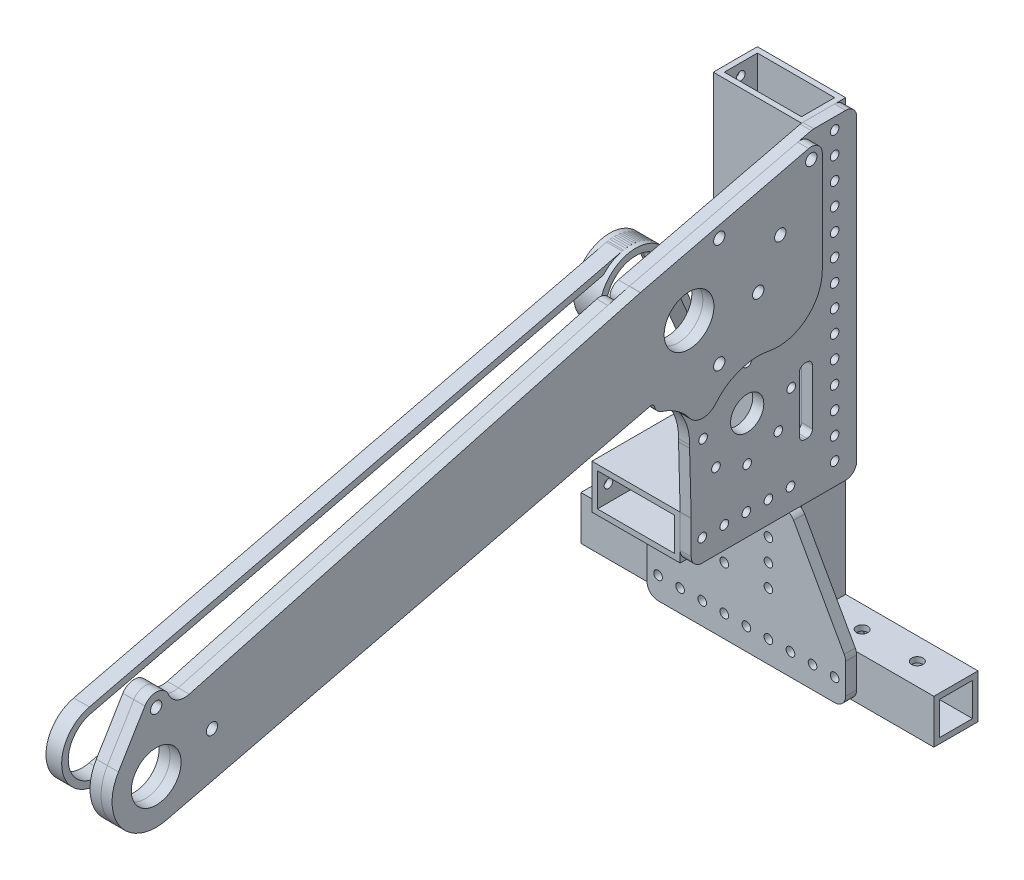
SolidWorks part; units mm, degrees
ref_plane "Alzado" through (0, 0, 0) normal (0, 0, 1) x (1, 0, 0)
ref_plane "Planta" through (0, 0, 0) normal (0, 1, 0) x (1, 0, 0)
ref_plane "Vista lateral" through (0, 0, 0) normal (1, 0, 0) x (0, 0, -1)
sketch "Croquis1" plane through (0, 0, 0) normal (0, 1, 0) x (1, 0, 0)
  line L1 (-101.6, -12.7) -> (101.6, -12.7)
  line L2 (-101.6, -12.7) -> (-101.6, 12.7)
  line L3 (-101.6, 12.7) -> (101.6, 12.7)
  line L4 (101.6, -12.7) -> (101.6, 12.7)
  line L5 (-101.6, -12.7) -> (101.6, 12.7) construction
  line L6 (-101.6, 12.7) -> (101.6, -12.7) construction
  point P0 (0, 0)
  dimension "D1" = 25.4
  dimension "D2" = 203.2
extrude "Saliente-Extruir1" add sketch "Croquis1" along normal blind 25.4
shell "Vaciado1" thickness 3.175 removed face at (-101.6, 12.7, 0) removed face at (101.6, 12.7, 0)
sketch "Croquis2" plane through (0, 25.4, 0) normal (0, 1, 0) x (1, 0, 0)
  line L0 (101.6, 12.7) -> (-101.6, 12.7) construction
  line L1 (-25.4, -12.7) -> (25.4, -12.7)
  line L2 (-25.4, -12.7) -> (-25.4, 12.7)
  line L3 (-25.4, 12.7) -> (25.4, 12.7)
  line L4 (25.4, -12.7) -> (25.4, 12.7)
  line L5 (-25.4, -12.7) -> (25.4, 12.7) construction
  line L6 (-25.4, 12.7) -> (25.4, -12.7) construction
  line L8 (-22.225, -9.525) -> (22.225, -9.525)
  line L9 (-22.225, -9.525) -> (-22.225, 9.525)
  line L10 (-22.225, 9.525) -> (22.225, 9.525)
  line L11 (22.225, -9.525) -> (22.225, 9.525)
  line L12 (-22.225, -9.525) -> (22.225, 9.525) construction
  line L13 (-22.225, 9.525) -> (22.225, -9.525) construction
  point P0 (0, 0)
  point P8 (0, 0)
  dimension "D1" = 50.8
  dimension "D2" = 3.175
  dimension "D3" = 3.175
extrude "Saliente-Extruir2" add sketch "Croquis2" along normal blind 247.65 separate body
sketch "Croquis3" plane through (0, 25.4, 0) normal (0, 1, 0) x (1, 0, 0)
  line L0 (0, 0) -> (0, 12.7) construction
  line L1 (25.4, 12.7) -> (-25.4, 12.7) construction
  circle A0 centre (-47.625, 0) radius 3.2639
  circle A1 centre (-79.375, 0) radius 3.2639
  circle A2 centre (79.375, 0) radius 3.2639
  circle A3 centre (47.625, 0) radius 3.2639
  dimension "D1" = 47.625
  dimension "D2" = 6.5278
  dimension "D3" = 31.75
extrude "Cortar-Extruir1" cut sketch "Croquis3" against normal through all
sketch "Croquis4" plane through (0, 0, 12.7) normal (0, 0, 1) x (1, 0, 0)
  line L0 (0, 25.4) -> (0, 139.6619) construction
  line L1 (-101.6, 25.4) -> (101.6, 25.4) construction
  line L2 (0, 139.6619) -> (-23.8125, 139.6619) construction
  circle A0 centre (0, 139.6619) radius 14.3129
  circle A1 centre (0, 139.6619) radius 23.8125 construction
  circle A2 centre (-23.8125, 139.6619) radius 2.4892 construction
  circle A3 centre (-11.9062, 160.2841) radius 2.4892
  circle A4 centre (11.9063, 160.2841) radius 2.4892
  circle A5 centre (23.8125, 139.6619) radius 2.4892 construction
  circle A6 centre (11.9062, 119.0397) radius 2.4892
  circle A7 centre (-11.9063, 119.0397) radius 2.4892
  dimension "D1" = 28.6258
  dimension "D3" = 47.625
  dimension "D4" = 4.9784
  dimension "D2" = 114.2619
  dimension "D6" = 23.8125
  dimension "D5" = 6
extrude "Cortar-Extruir2" cut sketch "Croquis4" against normal through all
sketch "Croquis8" plane through (0, 0, 12.7) normal (0, 0, 1) x (1, 0, 0)
  line L0 (0, 0) -> (0, 273.05) construction
  line L1 (-101.6, 12.7) -> (0, 12.7) construction
  line L2 (-101.6, 25.4) -> (-101.6, 0) construction
  line L3 (0, 12.7) -> (-12.7, 12.7) construction
  line L4 (0, 12.7) -> (12.7, 12.7) construction
  line L5 (-25.4, 273.05) -> (25.4, 273.05) construction
  line L6 (-12.7, 12.7) -> (-12.7, 25.4) construction
  circle A0 centre (0, 12.7) radius 2.4892
  circle A1 centre (-12.7, 12.7) radius 2.4892
  circle A2 centre (-25.4, 12.7) radius 2.4892
  circle A3 centre (-38.1, 12.7) radius 2.4892
  circle A4 centre (-50.8, 12.7) radius 2.4892
  circle A5 centre (0, 12.7) radius 2.4892
  circle A6 centre (-12.7, 12.7) radius 2.4892
  circle A7 centre (-25.4, 12.7) radius 2.4892
  circle A8 centre (-38.1, 12.7) radius 2.4892
  circle A9 centre (12.7, 12.7) radius 2.4892
  circle A10 centre (0, 12.7) radius 2.4892
  circle A11 centre (-12.7, 12.7) radius 2.4892
  circle A12 centre (-25.4, 12.7) radius 2.4892
  circle A13 centre (25.4, 12.7) radius 2.4892
  circle A14 centre (12.7, 12.7) radius 2.4892
  circle A15 centre (0, 12.7) radius 2.4892
  circle A16 centre (-12.7, 12.7) radius 2.4892
  circle A17 centre (38.1, 12.7) radius 2.4892
  circle A18 centre (25.4, 12.7) radius 2.4892
  circle A19 centre (12.7, 12.7) radius 2.4892
  circle A20 centre (0, 12.7) radius 2.4892
  circle A21 centre (12.7, 12.7) radius 2.4892
  circle A22 centre (25.4, 12.7) radius 2.4892
  circle A23 centre (38.1, 12.7) radius 2.4892
  circle A24 centre (50.8, 12.7) radius 2.4892
  circle A25 centre (-12.7, 25.4) radius 2.4892 [skipped]
  circle A26 centre (12.7, 25.4) radius 2.4892 [skipped]
  circle A27 centre (-12.7, 38.1) radius 2.4892
  circle A28 centre (12.7, 38.1) radius 2.4892
  circle A29 centre (-12.7, 50.8) radius 2.4892
  circle A30 centre (12.7, 50.8) radius 2.4892
  circle A31 centre (-12.7, 63.5) radius 2.4892
  circle A32 centre (12.7, 63.5) radius 2.4892
  circle A33 centre (-12.7, 76.2) radius 2.4892
  circle A34 centre (12.7, 76.2) radius 2.4892
  dimension "D1" = 4.9784
  dimension "D4" = 12.7
  dimension "D5" = 12.7
  dimension "D7" = 12.7
  dimension "D2" = 5
  dimension "D3" = 5
  dimension "D6" = 6
extrude "Cortar-Extruir4" cut sketch "Croquis8" against normal through all contours A4 | A3 | A2 | A1 | A0 | A9 | A13 | A17 | A24 | A28 | A29 | A30 | A31 | A32 | A34 | A33 | A27 region at (0, 12.7, 12.7) region at (-12.7, 12.7, 12.7) region at (-25.4, 12.7, 12.7) region at (-38.1, 12.7, 12.7) region at (-50.8, 12.7, 12.7) region at (12.7, 12.7, 12.7) region at (25.4, 12.7, 12.7) region at (38.1, 12.7, 12.7) region at (50.8, 12.7, 12.7) region at (12.7, 38.1, 12.7) region at (-12.7, 50.8, 12.7) region at (12.7, 50.8, 12.7) region at (-12.7, 63.5, 12.7) region at (12.7, 63.5, 12.7) region at (-12.7, 76.2, 12.7) region at (12.7, 76.2, 12.7)
sketch "Croquis6" plane through (0, 0, 12.7) normal (0, 0, 1) x (1, 0, 0)
  line L0 (25.4, 273.05) -> (25.4, 25.4) construction
  line L1 (-25.4, 88.646) -> (25.4, 88.646)
  line L2 (-25.4, 88.646) -> (-25.4, 114.046)
  line L3 (-25.4, 114.046) -> (25.4, 114.046)
  line L4 (25.4, 88.646) -> (25.4, 114.046)
  line L5 (-25.4, 88.646) -> (25.4, 114.046) construction
  line L6 (-25.4, 114.046) -> (25.4, 88.646) construction
  line L7 (-101.6, 25.4) -> (101.6, 25.4) construction
  line L9 (-22.225, 91.821) -> (22.225, 91.821)
  line L10 (-22.225, 91.821) -> (-22.225, 110.871)
  line L11 (-22.225, 110.871) -> (22.225, 110.871)
  line L12 (22.225, 91.821) -> (22.225, 110.871)
  line L13 (-22.225, 91.821) -> (22.225, 110.871) construction
  line L14 (-22.225, 110.871) -> (22.225, 91.821) construction
  point P0 (0, 101.346)
  point P11 (0, 101.346)
  dimension "D1" = 25.4
  dimension "D2" = 63.246
  dimension "D3" = 3.175
  dimension "D4" = 3.175
extrude "Saliente-Extruir3" add sketch "Croquis6" along normal blind 69.85 separate body
sketch "Croquis7" plane through (0, 114.046, 0) normal (0, 1, 0) x (1, 0, 0)
  line L0 (0, -12.7) -> (0, -82.55) construction
  line L1 (-25.4, -12.7) -> (25.4, -12.7) construction
  line L2 (25.4, -82.55) -> (-25.4, -82.55) construction
  line L3 (16.51, -12.7) -> (-16.51, -12.7)
  line L4 (25.4, -12.7) -> (-25.4, -12.7) construction
  line L5 (-16.51, -12.7) -> (-16.51, -34.798)
  line L6 (-13.208, -38.1) -> (13.208, -38.1)
  line L7 (16.51, -12.7) -> (16.51, -34.798)
  arc A0 (16.51, -34.798) -> (13.208, -38.1) centre (13.208, -34.798) cw
  arc A1 (-16.51, -34.798) -> (-13.208, -38.1) centre (-13.208, -34.798) ccw
  point P12 (0, -38.1)
  point P16 (16.51, -38.1)
  point P19 (-16.51, -38.1)
  dimension "D3" = 3.302
  dimension "D1" = 25.4
  dimension "D2" = 33.02
extrude "Cortar-Extruir3" cut sketch "Croquis7" against normal up to next (3.175 mm away)
sketch "Croquis11" plane through (25.4, 0, 0) normal (1, 0, 0) x (0, 0, -1)
  line L0 (0, -101.854) -> (-381, -101.854) construction
  line L1 (-82.55, 88.646) -> (-82.55, 114.046) construction
  line L2 (-82.55, 88.646) -> (-12.7, 88.646) construction
  line L6 (-517.96, -101.854) -> (-276.66, -101.854) construction
  line L7 (-517.96, -101.854) -> (-517.96, 139.446) construction
  line L8 (-517.96, 139.446) -> (-276.66, 139.446) construction
  line L9 (-276.66, -101.854) -> (-276.66, 139.446) construction
  circle A0 centre (-396.875, 145.796) radius 38.1
  dimension "D3" = 76.2
  dimension "D4" = 209.55
  dimension "D5" = 276.225
  dimension "D1" = 190.5
  dimension "D2" = 381
  dimension "D6" = 241.3
sketch "Croquis9" plane through (0, 0, 12.7) normal (0, 0, 1) x (1, 0, 0)
  line L0 (0, 0) -> (0, 273.05) construction
  line L1 (-25.4, 273.05) -> (25.4, 273.05) construction
  line L2 (50.8, 0) -> (-50.8, 0)
  line L3 (-101.6, 0) -> (101.6, 0) construction
  line L4 (-57.15, 6.35) -> (-57.15, 23.7481)
  line L5 (-101.6, 25.4) -> (101.6, 25.4) construction
  line L6 (-56.3451, 26.8425) -> (-27.2168, 79.0403)
  line L7 (-25.4, 273.05) -> (-25.4, 25.4) construction
  line L8 (-21.6717, 82.296) -> (21.6717, 82.296)
  line L9 (56.3451, 26.8425) -> (27.2168, 79.0403)
  line L10 (57.15, 6.35) -> (57.15, 23.7481)
  line L11 (-25.4, 88.646) -> (25.4, 88.646) construction
  circle A0 centre (-50.8, 12.7) radius 2.4892 construction
  arc A2 (-50.8, 0) -> (-57.15, 6.35) centre (-50.8, 6.35) cw
  arc A3 (-57.15, 23.7481) -> (-56.3451, 26.8425) centre (-50.8, 23.7481) cw
  arc A4 (-27.2168, 79.0403) -> (-21.6717, 82.296) centre (-21.6717, 75.946) cw
  arc A5 (27.2168, 79.0403) -> (21.6717, 82.296) centre (21.6717, 75.946) ccw
  arc A6 (57.15, 23.7481) -> (56.3451, 26.8425) centre (50.8, 23.7481) ccw
  arc A7 (50.8, 0) -> (57.15, 6.35) centre (50.8, 6.35) ccw
  circle A9 centre (-25.4, 12.7) radius 2.4892
  circle A10 centre (-25.4, 12.7) radius 2.4892
  circle A11 centre (-12.7, 12.7) radius 2.4892
  circle A12 centre (-12.7, 12.7) radius 2.4892
  circle A13 centre (0, 12.7) radius 2.4892
  circle A14 centre (0, 12.7) radius 2.4892
  circle A15 centre (0, 12.7) radius 2.4892
  circle A16 centre (0, 12.7) radius 2.4892
  circle A17 centre (12.7, 12.7) radius 2.4892
  circle A18 centre (12.7, 12.7) radius 2.4892
  circle A19 centre (-38.1, 12.7) radius 2.4892
  circle A20 centre (-38.1, 12.7) radius 2.4892
  circle A21 centre (-25.4, 12.7) radius 2.4892
  circle A22 centre (-25.4, 12.7) radius 2.4892
  circle A23 centre (-12.7, 12.7) radius 2.4892
  circle A24 centre (-12.7, 12.7) radius 2.4892
  circle A25 centre (0, 12.7) radius 2.4892
  circle A26 centre (0, 12.7) radius 2.4892
  circle A27 centre (-50.8, 12.7) radius 2.4892
  circle A28 centre (-50.8, 12.7) radius 2.4892
  circle A29 centre (-38.1, 12.7) radius 2.4892
  circle A30 centre (-38.1, 12.7) radius 2.4892
  circle A31 centre (25.4, 12.7) radius 2.4892
  circle A32 centre (25.4, 12.7) radius 2.4892
  circle A33 centre (38.1, 12.7) radius 2.4892
  circle A34 centre (38.1, 12.7) radius 2.4892
  circle A35 centre (-12.7, 12.7) radius 2.4892
  circle A36 centre (-12.7, 12.7) radius 2.4892
  circle A37 centre (0, 12.7) radius 2.4892
  circle A38 centre (0, 12.7) radius 2.4892
  circle A39 centre (12.7, 12.7) radius 2.4892
  circle A40 centre (12.7, 12.7) radius 2.4892
  circle A41 centre (25.4, 12.7) radius 2.4892
  circle A42 centre (25.4, 12.7) radius 2.4892
  circle A43 centre (-25.4, 12.7) radius 2.4892
  circle A44 centre (-25.4, 12.7) radius 2.4892
  circle A45 centre (-12.7, 12.7) radius 2.4892
  circle A46 centre (-12.7, 12.7) radius 2.4892
  circle A47 centre (50.8, 12.7) radius 2.4892
  circle A48 centre (50.8, 12.7) radius 2.4892
  circle A49 centre (38.1, 12.7) radius 2.4892
  circle A50 centre (38.1, 12.7) radius 2.4892
  circle A51 centre (25.4, 12.7) radius 2.4892
  circle A52 centre (25.4, 12.7) radius 2.4892
  circle A53 centre (12.7, 12.7) radius 2.4892
  circle A54 centre (12.7, 12.7) radius 2.4892
  circle A55 centre (0, 12.7) radius 2.4892
  circle A56 centre (0, 12.7) radius 2.4892
  circle A57 centre (12.7, 12.7) radius 2.4892
  circle A58 centre (12.7, 12.7) radius 2.4892
  circle A59 centre (-12.7, 76.2) radius 2.4892
  circle A60 centre (-12.7, 76.2) radius 2.4892
  circle A61 centre (12.7, 63.5) radius 2.4892
  circle A62 centre (12.7, 63.5) radius 2.4892
  circle A63 centre (-12.7, 63.5) radius 2.4892
  circle A64 centre (-12.7, 63.5) radius 2.4892
  circle A65 centre (12.7, 50.8) radius 2.4892
  circle A66 centre (12.7, 50.8) radius 2.4892
  circle A67 centre (-12.7, 50.8) radius 2.4892
  circle A68 centre (-12.7, 50.8) radius 2.4892
  circle A69 centre (12.7, 38.1) radius 2.4892
  circle A70 centre (12.7, 38.1) radius 2.4892
  circle A71 centre (-12.7, 38.1) radius 2.4892
  circle A72 centre (-12.7, 38.1) radius 2.4892
  circle A73 centre (12.7, 76.2) radius 2.4892
  circle A74 centre (12.7, 76.2) radius 2.4892
  point P22 (-57.15, 0)
  point P25 (-57.15, 25.4)
  point P28 (-25.4, 82.296)
  point P38 (0, 82.296)
  circle M37 centre (-50.8, 12.7) radius 2.4892
  circle M38 centre (-38.1, 12.7) radius 2.4892
  circle M39 centre (-25.4, 12.7) radius 2.4892
  circle M40 centre (-12.7, 12.7) radius 2.4892
  circle M41 centre (0, 12.7) radius 2.4892
  circle M42 centre (12.7, 12.7) radius 2.4892
  circle M43 centre (25.4, 12.7) radius 2.4892
  circle M44 centre (38.1, 12.7) radius 2.4892
  circle M45 centre (50.8, 12.7) radius 2.4892
  line M46 (-101.6, 0) -> (101.6, 0)
  line M48 (101.6, 25.4) -> (-101.6, 25.4)
  dimension "D1" = 6.35
  dimension "D3" = 6.35
  dimension "D37" = 6.35
  dimension "D4" = 0
  dimension "D5" = 0
  dimension "D6" = 0
  dimension "D7" = 0
  dimension "D8" = 0
  dimension "D9" = 0
  dimension "D10" = 0
  dimension "D11" = 0
  dimension "D12" = 0
  dimension "D13" = 0
  dimension "D14" = 0
  dimension "D15" = 0
  dimension "D16" = 0
  dimension "D17" = 0
  dimension "D18" = 0
  dimension "D19" = 0
  dimension "D20" = 0
  dimension "D21" = 0
  dimension "D22" = 0
  dimension "D23" = 0
  dimension "D24" = 0
  dimension "D25" = 0
  dimension "D26" = 0
  dimension "D27" = 0
  dimension "D28" = 0
  dimension "D29" = 0
  dimension "D30" = 0
  dimension "D31" = 0
  dimension "D32" = 0
  dimension "D33" = 0
  dimension "D34" = 0
  dimension "D35" = 0
  dimension "D36" = 0
extrude "Saliente-Extruir4" add sketch "Croquis9" along normal blind 6.35 separate body contours L0 L8 A4 L6 A3 A60 A64 A68 A72 M48 | L0 A6 L9 A5 L8 A74 A70 A66 A62 M48 | L0 A3 L4 A2 M46 M41 M48 M37 M39 M40 M38 | L0 L2 A7 L10 A6 A56 M48 M42 M44 M45 M43 region at (-28.4143, 12.7709, 12.7) region at (28.4143, 12.7709, 12.7) region at (-21.9575, 49.932, 12.7) region at (21.9575, 49.932, 12.7)
sketch "Croquis15" plane through (25.4, 0, 0) normal (1, 0, 0) x (0, 0, -1)
  line L0 (-12.7, 0) -> (-12.7, 171.1325) construction
  line L1 (-12.7, 273.05) -> (-12.7, 25.4) construction
  line L2 (-72.5746, 227.1642) -> (-41.5317, 154.1315) construction
  line L3 (-105.4538, 208.2656) -> (-57.9713, 144.6822) construction
  line L4 (-94.6246, 238.2605) -> (-401.3483, 164.3633) construction
  line L5 (-392.4017, 127.2287) -> (-85.6779, 201.1258) construction
  line L8 (-82.55, 114.046) -> (-12.7, 114.046) construction
  circle A0 centre (-50.32, 150.396) radius 30
  arc A1 (-57.9713, 144.6822) -> (-41.5317, 154.1315) centre (-50.32, 150.396) ccw construction
  arc A2 (-401.3483, 164.3633) -> (-392.4017, 127.2287) centre (-396.875, 145.796) ccw construction
  arc A3 (-72.5746, 227.1642) -> (-105.4538, 208.2656) centre (-90.1513, 219.6932) ccw construction
  arc A4 (-85.6779, 201.1258) -> (-94.6246, 238.2605) centre (-90.1513, 219.6932) ccw construction
  dimension "D2" = 60
  dimension "D3" = 19.0986
  dimension "D4" = 38.1972
  dimension "D1" = 171.1325
  dimension "D7" = 6.35
  dimension "D8" = 7.62
sketch "Croquis16" plane through (25.4, 0, 0) normal (1, 0, 0) x (0, 0, -1)
  line L0 (-50.32, 150.396) -> (-50.32, 175.796) construction
  line L1 (-13.4332, 272.8734) -> (-118.1525, 247.644)
  line L2 (-82.55, 94.996) -> (-82.55, 113.9625)
  line L3 (-82.5522, 114.1295) -> (-83.4835, 149.5234)
  line L4 (-76.2, 88.646) -> (6.35, 88.646)
  line L5 (12.7, 273.05) -> (12.7, 25.4) construction
  line L6 (12.7, 94.996) -> (12.7, 266.7)
  line L7 (6.35, 273.05) -> (-11.9459, 273.05)
  line L8 (-94.6246, 238.2605) -> (-401.3483, 164.3633) construction
  line L9 (-122.8385, 239.9833) -> (-110.0117, 186.743)
  line L10 (-90.1513, 219.6932) -> (-116.4251, 213.3632) construction
  circle A0 centre (-90.1513, 219.6932) radius 14.3256
  circle A1 centre (-50.32, 150.396) radius 33.175
  circle A4 centre (-50.32, 150.396) radius 9.5631
  circle A5 centre (-50.32, 150.396) radius 25.4 construction
  circle A6 centre (-50.32, 175.796) radius 2.4892
  circle A7 centre (-32.3595, 168.3565) radius 2.4892 construction
  circle A8 centre (-24.92, 150.396) radius 2.4892
  circle A9 centre (-32.3595, 132.4355) radius 2.4892
  circle A10 centre (-50.32, 124.996) radius 2.4892
  circle A11 centre (-68.2805, 132.4355) radius 2.4892
  circle A12 centre (-75.72, 150.396) radius 2.4892
  circle A13 centre (-68.2805, 168.3565) radius 2.4892
  arc A18 (-105.7366, 182.1707) -> (-83.4864, 151.1506) centre (-115.2282, 151.8727) cw
  arc A19 (-110.0117, 186.743) -> (-105.7366, 182.1707) centre (-103.8383, 188.2304) ccw
  arc A21 (-118.1525, 247.644) -> (-122.8385, 239.9833) centre (-116.6652, 241.4706) ccw
  arc A23 (-11.9459, 273.05) -> (-13.4332, 272.8734) centre (-11.9459, 266.7) ccw
  circle A26 centre (-50.32, 150.396) radius 30 construction
  arc A29 (-82.55, 113.9625) -> (-82.5522, 114.1295) centre (-88.9, 113.9625) ccw
  arc A31 (12.7, 266.7) -> (6.35, 273.05) centre (6.35, 266.7) ccw
  arc A32 (6.35, 88.646) -> (12.7, 94.996) centre (6.35, 94.996) ccw
  arc A33 (-82.55, 94.996) -> (-76.2, 88.646) centre (-76.2, 94.996) ccw
  point P45 (-12.7, 273.05)
  point P72 (-82.55, 114.046)
  point P74 (12.7, 273.05)
  point P77 (12.7, 88.646)
  point P80 (-82.55, 88.646)
  line M2 (12.7, 25.4) -> (12.7, 273.05)
  line M3 (12.7, 273.05) -> (-12.7, 273.05)
  line M4 (-12.7, 273.05) -> (-12.7, 25.4)
  dimension "D1" = 28.6512
  dimension "D2" = 3.175
  dimension "D3" = 31.75
  dimension "D4" = 19.1262
  dimension "D5" = 50.8
  dimension "D6" = 4.9784
  dimension "D9" = 6.35
  dimension "D10" = 6.35
  dimension "D14" = 6.35
  dimension "D15" = 6.35
  dimension "D12" = 6.35
  dimension "D8" = 25.4
  dimension "D11" = 12.7
  dimension "D7" = 8
extrude "Saliente-Extruir5" add sketch "Croquis16" along normal blind 6.35 separate body contours L4 A32 A31 A23 M2 M3 M4 | L2 A33 L4 A23 L1 A21 L9 A19 A18 A1 L3 A29 A0 M4 | A1 A13 A12 A11 A10 A9 A8 A6 A4 region at (25.4, 191.9467, 55.8371) region at (25.4, 180.8478, 0.0418) region at (25.4, 182.6306, 49.9534)
sketch "Croquis12" plane through (25.4, 0, 0) normal (1, 0, 0) x (0, 0, -1)
  line L0 (-82.55, 101.346) -> (-12.7, 101.346) construction
  line L1 (-82.55, 88.646) -> (-82.55, 114.046) construction
  line L2 (-12.7, 88.646) -> (-12.7, 114.046) construction
  line L3 (0, 273.05) -> (0, 0) construction
  line L4 (-12.7, 273.05) -> (12.7, 273.05) construction
  line L5 (0, 101.346) -> (-12.7, 101.346) construction
  line L6 (0, 101.346) -> (0, 114.046) construction
  circle A1 centre (0, 101.346) radius 2.4892
  circle A2 centre (-12.7, 101.346) radius 2.4892 [skipped]
  circle A3 centre (-25.4, 101.346) radius 2.4892
  circle A4 centre (-38.1, 101.346) radius 2.4892
  circle A5 centre (-50.8, 101.346) radius 2.4892
  circle A6 centre (0, 114.046) radius 2.4892
  circle A7 centre (0, 126.746) radius 2.4892
  circle A8 centre (0, 139.446) radius 2.4892
  circle A9 centre (0, 152.146) radius 2.4892
  circle A10 centre (0, 164.846) radius 2.4892
  circle A11 centre (0, 177.546) radius 2.4892
  circle A12 centre (0, 190.246) radius 2.4892
  circle A13 centre (0, 202.946) radius 2.4892
  circle A14 centre (0, 215.646) radius 2.4892
  circle A15 centre (0, 228.346) radius 2.4892
  circle A16 centre (0, 241.046) radius 2.4892
  circle A17 centre (0, 253.746) radius 2.4892
  circle A18 centre (0, 266.446) radius 2.4892
  circle A19 centre (-63.5, 101.346) radius 2.4892
  circle A20 centre (-76.2, 101.346) radius 2.4892
  dimension "D1" = 4.9784
  dimension "D3" = 12.7
  dimension "D5" = 12.7
  dimension "D2" = 7
  dimension "D4" = 14
extrude "Cortar-Extruir5" cut sketch "Croquis12" against normal through all and the other way through all
sketch "Croquis17" plane through (31.75, 0, 0) normal (1, 0, 0) x (0, 0, -1)
  line L0 (-403.5186, 170.3118) -> (-118.2389, 247.6205)
  line L1 (-118.0654, 247.6649) -> (-21.2705, 270.9852)
  line L2 (-390.9258, 121.1026) -> (-118.1525, 186.8202)
  line L3 (-392.4017, 127.2287) -> (-85.6779, 201.1258) construction
  line L4 (-118.1525, 186.8202) -> (-112.4025, 188.2055)
  line L5 (-13.4332, 206.3797) -> (-13.4332, 264.8118)
  line L7 (-403.3993, 184.1476) -> (-418.6226, 158.9186)
  circle A0 centre (-396.875, 145.796) radius 14.3256
  circle A1 centre (-90.1513, 219.6932) radius 14.3256
  circle A2 centre (-396.875, 145.796) radius 25.4
  arc A3 (-118.2389, 247.6205) -> (-118.0654, 247.6649) centre (-116.578, 241.4916) cw
  arc A4 (-21.2705, 270.9852) -> (-13.4332, 264.8118) centre (-19.7832, 264.8118) cw
  arc A5 (-13.4332, 206.3797) -> (-43.9384, 181.4981) centre (-38.8332, 206.3797) cw
  circle A6 centre (-50.32, 150.396) radius 31.75
  arc A8 (-110.0117, 186.743) -> (-105.7366, 182.1707) centre (-103.8383, 188.2304) ccw construction
  arc A9 (-110.0117, 186.743) -> (-105.7366, 182.1707) centre (-103.8383, 188.2304) ccw
  arc A10 (-110.0117, 186.743) -> (-112.4025, 188.2055) centre (-111.9383, 186.2789) ccw
  arc A11 (-83.4864, 151.1506) -> (-105.7366, 182.1707) centre (-115.2282, 151.8727) ccw construction
  arc A12 (-89.8175, 170.9084) -> (-105.7366, 182.1707) centre (-115.2282, 151.8727) ccw
  arc A13 (-89.8175, 170.9084) -> (-74.8387, 170.5677) centre (-82.1943, 176.6192) ccw
  circle A14 centre (-396.875, 180.2108) radius 7.62
  arc A16 (-389.8471, 183.1558) -> (-377.8191, 177.2761) centre (-380.4766, 187.0824) ccw
  point P19 (-118.1525, 247.644)
  point P23 (-13.4332, 272.8734)
  line M28 (-13.4332, 272.8734) -> (-118.1525, 247.644)
  arc M29 (-118.1525, 247.644) -> (-122.8385, 239.9833) centre (-116.6652, 241.4706) ccw
  line M30 (-122.8385, 239.9833) -> (-110.0117, 186.743)
  circle M38 centre (-90.1513, 219.6932) radius 14.3256
  dimension "D1" = 28.6512
  dimension "D2" = 50.8
  dimension "D3" = 6.35
  dimension "D4" = 63.5
  dimension "D5" = 9.525
  dimension "D6" = 25.4
  dimension "D7" = 15.24
  dimension "D8" = 34.4148
  dimension "D9" = 10.16
extrude "Saliente-Extruir6" add sketch "Croquis17" along normal blind 6.35 separate body contours A2 L2 L0 M30 M29 | L5 A4 A3 L0 M28 M29 M30 M38 | A2 A0 | A16 A14 L7 A2 L0 | A14 M30 region at (31.75, 173.536, 401.4081) region at (31.75, 184.8147, 244.5216) region at (31.75, 165.3985, 381.8776) region at (31.75, 220.7032, 61.6214) region at (31.75, 180.2108, 396.875)
sketch "Croquis18" plane through (38.1, 0, 0) normal (1, 0, 0) x (0, 0, -1)
  line L0 (-122.8385, 239.9833) -> (-110.0117, 186.743) construction
  line L1 (-122.754, 239.6323) -> (-111.9631, 194.8431)
  line L2 (-403.5186, 170.3118) -> (-118.2389, 247.6205) construction
  line L3 (-403.3993, 184.1476) -> (-418.6226, 158.9186) construction
  line L5 (-403.3993, 184.1476) -> (-418.6226, 158.9186)
  line L6 (-390.9258, 121.1026) -> (-118.1525, 186.8202) construction
  line L7 (-403.5186, 170.3118) -> (-130.5882, 244.274)
  line L10 (-122.8385, 239.9833) -> (-110.0117, 186.743) construction
  line L11 (-390.9258, 121.1026) -> (-116.6492, 187.1824)
  circle A1 centre (-396.875, 145.796) radius 25.4
  circle A2 centre (-396.875, 145.796) radius 25.4
  arc A3 (-116.6492, 187.1824) -> (-111.9631, 194.8431) centre (-118.1365, 193.3558) ccw
  circle A5 centre (-396.875, 145.796) radius 14.3256
  circle A6 centre (-396.875, 145.796) radius 14.3256
  arc A12 (-122.754, 239.6323) -> (-130.5882, 244.274) centre (-128.9273, 238.145) ccw
  arc A13 (-389.8471, 183.1558) -> (-377.8191, 177.2761) centre (-380.4766, 187.0824) ccw construction
  circle A14 centre (-396.875, 180.2108) radius 7.62 construction
  arc A15 (-389.8471, 183.1558) -> (-377.8191, 177.2761) centre (-380.4766, 187.0824) ccw
  circle A16 centre (-396.875, 180.2108) radius 7.62
  point P18 (-110.4758, 188.6697)
  line M10 (-118.2389, 247.6205) -> (-377.8191, 177.2761)
  arc M11 (-418.6226, 158.9186) -> (-390.9258, 121.1026) centre (-396.875, 145.796) ccw
  circle M13 centre (-396.875, 145.796) radius 14.3256
  line M33 (-403.3993, 184.1476) -> (-418.6226, 158.9186)
  arc M34 (-377.8191, 177.2761) -> (-389.8471, 183.1558) centre (-380.4766, 187.0824) cw
  arc M35 (-389.8471, 183.1558) -> (-403.3993, 184.1476) centre (-396.875, 180.2108) ccw
  dimension "D2" = 6.35
  dimension "D1" = 0
  dimension "D3" = 0
extrude "Saliente-Extruir7" add sketch "Croquis18" along normal blind 6.35 from surface separate body contours L1 A12 A2 A3 M10 | A2 M11 M13 | A16 A2 L7 M33 M34 | A16 M35 region at (38.1, 184.7417, 244.7476) region at (38.1, 173.536, 401.4081) region at (38.1, 131.2122, 416.7871) region at (38.1, 180.2108, 396.875) starting at face at (25.4, 101.346, -2.4892)
sketch "Croquis22" plane through (38.1, 0, 0) normal (1, 0, 0) x (0, 0, -1)
  line L0 (-396.875, 145.796) -> (-90.1513, 219.6932) construction
  line L1 (-90.1513, 219.6932) -> (-50.32, 150.396) construction
  line L4 (-50.32, 236.121) -> (-37.62, 236.121) construction
  line L5 (-21.2705, 270.9852) -> (-118.0654, 247.6649) construction
  circle A0 centre (-396.875, 180.2108) radius 3.2639
  circle A1 centre (-364.7735, 153.53) radius 3.2639
  circle A2 centre (-396.875, 145.796) radius 19.0986 construction
  arc A3 (-401.3483, 164.3633) -> (-392.4017, 127.2287) centre (-396.875, 145.796) ccw construction
  circle A4 centre (-364.7735, 153.53) radius 6.35 construction
  circle A7 centre (-72.747, 189.4137) radius 3.2639
  circle A8 centre (-72.747, 189.4137) radius 6.35 construction
  circle A9 centre (-50.32, 213.896) radius 6.35 construction
  circle A10 centre (-50.32, 213.896) radius 3.2639
  circle A13 centre (-37.62, 236.121) radius 3.2639
  circle A14 centre (-37.62, 236.121) radius 6.35 construction
  circle A15 centre (-72.747, 252.0515) radius 3.2639
  circle A16 centre (-72.747, 252.0515) radius 6.35 construction
  circle A17 centre (-19.7832, 264.8118) radius 6.35 construction
  circle A18 centre (-19.7832, 264.8118) radius 3.2639
  dimension "D1" = 6.5278
  dimension "D2" = 33.02
  dimension "D3" = 12.7
  dimension "D4" = 34.925
  dimension "D5" = 63.5
  dimension "D6" = 22.225
  dimension "D7" = 12.7
extrude "Cortar-Extruir6" cut sketch "Croquis22" against normal through all
sketch "Croquis24" plane through (38.1, 0, 0) normal (1, 0, 0) x (0, 0, -1)
  line L0 (-396.875, 145.796) -> (-90.1513, 219.6932) construction
  line L1 (-243.5131, 182.7446) -> (-247.9864, 201.3119) construction
  line L2 (-94.6246, 238.2605) -> (-401.3483, 164.3633) construction
  circle A0 centre (-295.9867, 170.1024) radius 2.4892
  circle A1 centre (-191.0395, 195.3867) radius 2.4892
  dimension "D1" = 4.9784
  dimension "D2" = 53.975
sketch "Croquis25" plane through (31.75, 0, 0) normal (1, 0, 0) x (0, 0, -1)
  line L0 (-12.7, 0) -> (-12.7, 139.7) construction
  line L1 (-12.7, 123.825) -> (-12.7, 155.575)
  line L2 (-12.7, 0) -> (-12.7, 171.1325) construction
  line L3 (-15.875, 158.75) -> (-17.145, 158.75)
  line L4 (-20.32, 155.575) -> (-20.32, 123.825)
  line L5 (-12.7, 139.7) -> (-20.32, 139.7) construction
  line L6 (-15.875, 120.65) -> (-17.145, 120.65)
  arc A0 (-12.7, 155.575) -> (-15.875, 158.75) centre (-15.875, 155.575) ccw
  arc A1 (-15.875, 120.65) -> (-12.7, 123.825) centre (-15.875, 123.825) ccw
  arc A2 (-17.145, 120.65) -> (-20.32, 123.825) centre (-17.145, 123.825) cw
  arc A3 (-17.145, 158.75) -> (-20.32, 155.575) centre (-17.145, 155.575) ccw
  point P13 (-12.7, 158.75)
  point P16 (-12.7, 120.65)
  point P19 (-20.32, 120.65)
  point P22 (-20.32, 158.75)
  dimension "D4" = 3.175
  dimension "D1" = 139.7
  dimension "D2" = 7.62
  dimension "D3" = 38.1
extrude "Cortar-Extruir8" cut sketch "Croquis25" against normal through all
delete or keep bodies "Sólido-Eliminar/Conservar 1" [suppressed] type keep bodies bodies 112
delete or keep bodies "Sólido-Eliminar/Conservar 2" [suppressed] type keep bodies bodies 111
delete or keep bodies "Sólido-Eliminar/Conservar 3" [suppressed] type keep bodies bodies 107
delete or keep bodies "Sólido-Eliminar/Conservar 4" [suppressed] type keep bodies bodies 109
delete or keep bodies "Sólido-Eliminar/Conservar 5" [suppressed] type keep bodies bodies 121
delete or keep bodies "Sólido-Eliminar/Conservar 6" [suppressed] type keep bodies bodies 119
sketch "Croquis29" plane through (0, 0, 0) normal (1, 0, 0) x (0, 0, -1)
  line L0 (-392.4017, 127.2287) -> (-85.6779, 201.1258) construction
  line L1 (-94.6246, 238.2605) -> (-401.3483, 164.3633) construction
  line L2 (-392.4017, 127.2287) -> (-85.6779, 201.1258) construction
  line L3 (-94.6246, 238.2605) -> (-401.3483, 164.3633) construction
  line L4 (-392.8842, 129.2314) -> (-86.1604, 203.1285)
  line L5 (-94.1421, 236.2578) -> (-400.8658, 162.3606)
  line L6 (-391.9941, 125.5371) -> (-85.2704, 199.4342)
  line L7 (-95.0321, 239.9521) -> (-401.7559, 166.0549)
  arc A0 (-85.6779, 201.1258) -> (-94.6246, 238.2605) centre (-90.1513, 219.6932) ccw construction
  arc A1 (-401.3483, 164.3633) -> (-392.4017, 127.2287) centre (-396.875, 145.796) ccw construction
  arc A2 (-85.6779, 201.1258) -> (-94.6246, 238.2605) centre (-90.1513, 219.6932) ccw construction
  arc A3 (-401.3483, 164.3633) -> (-392.4017, 127.2287) centre (-396.875, 145.796) ccw construction
  arc A4 (-86.1604, 203.1285) -> (-94.1421, 236.2578) centre (-90.1513, 219.6932) ccw
  arc A5 (-400.8658, 162.3606) -> (-392.8842, 129.2314) centre (-396.875, 145.796) ccw
  arc A6 (-401.7559, 166.0549) -> (-391.9941, 125.5371) centre (-396.875, 145.796) ccw
  arc A7 (-85.2704, 199.4342) -> (-95.0321, 239.9521) centre (-90.1513, 219.6932) ccw
  dimension "D1" = 2.06
  dimension "D2" = 3.8
extrude "Saliente-Extruir9" add sketch "Croquis29" along normal mid plane 9 separate body
sketch "Croquis30" plane through (0, 0, 0) normal (1, 0, 0) x (0, 0, -1)
  line L0 (-72.5746, 227.1642) -> (-41.5317, 154.1315) construction
  line L1 (-105.4538, 208.2656) -> (-57.9713, 144.6822) construction
  line L2 (-72.5746, 227.1642) -> (-41.5317, 154.1315) construction
  line L3 (-105.4538, 208.2656) -> (-57.9713, 144.6822) construction
  line L4 (-74.4704, 226.3584) -> (-43.4275, 153.3257)
  line L5 (-103.8032, 209.4982) -> (-56.3207, 145.9148)
  line L6 (-106.8479, 207.2245) -> (-59.3654, 143.6411)
  line L7 (-70.9732, 227.8449) -> (-39.9303, 154.8122)
  arc A0 (-57.9713, 144.6822) -> (-41.5317, 154.1315) centre (-50.32, 150.396) ccw construction
  arc A1 (-72.5746, 227.1642) -> (-105.4538, 208.2656) centre (-90.1513, 219.6932) ccw construction
  arc A2 (-57.9713, 144.6822) -> (-41.5317, 154.1315) centre (-50.32, 150.396) ccw construction
  arc A3 (-72.5746, 227.1642) -> (-105.4538, 208.2656) centre (-90.1513, 219.6932) ccw construction
  arc A4 (-56.3207, 145.9148) -> (-43.4275, 153.3257) centre (-50.32, 150.396) ccw
  arc A5 (-74.4704, 226.3584) -> (-103.8032, 209.4982) centre (-90.1513, 219.6932) ccw
  arc A6 (-70.9732, 227.8449) -> (-106.8479, 207.2245) centre (-90.1513, 219.6932) ccw
  arc A7 (-59.3654, 143.6411) -> (-39.9303, 154.8122) centre (-50.32, 150.396) ccw
  dimension "D1" = 2.06
  dimension "D2" = 3.8
extrude "Saliente-Extruir10" add sketch "Croquis30" along normal mid plane 15 separate body
delete or keep bodies "Sólido-Eliminar/Conservar 7" [suppressed] type keep bodies bodies 123
delete or keep bodies "Sólido-Eliminar/Conservar 8" [suppressed] type keep bodies bodies 124
equation "\"D1@Croquis15\"=5.5500+1.1875pulgadas"
equation "\"D3@Croquis15\"=(12*5mm)/pi"
equation "\"D4@Croquis15\"=(24*5mm)/pi"
equation "\"D5@Croquis15\"=(50*5mm)+1mm"
equation "\"D6@Croquis15\"=(150*5mm)+1mm"
